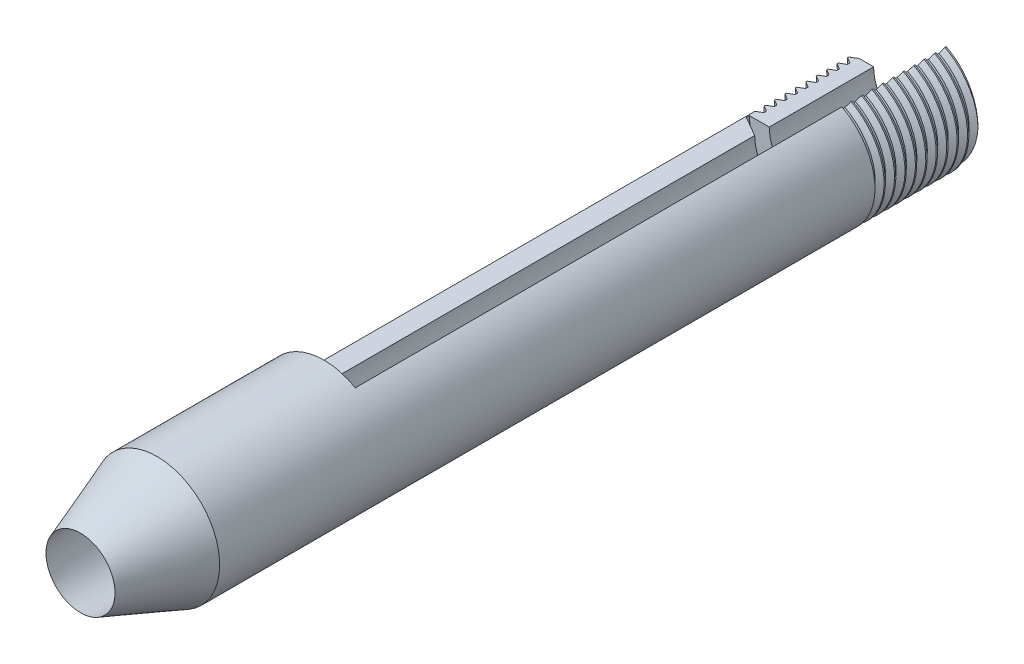
SolidWorks part; units mm, degrees
note: The reader was unsure of these and kept them because the rebuilt part matched: shared geometry of "Sketch2<8>", "Sketch2<12>".
ref_plane "Front Plane" through (0, 0, 0) normal (0, 0, 1) x (1, 0, 0)
ref_plane "Top Plane" through (0, 0, 0) normal (0, 1, 0) x (1, 0, 0)
ref_plane "Right Plane" through (0, 0, 0) normal (1, 0, 0) x (0, 0, -1)
sketch "Sketch2" plane through (0, 0, 0) normal (0, 1, 0) x (1, 0, 0)
  line L1 (-9, 0) -> (-9, -108.9955)
  line L2 (-4.958, -119.9955) -> (-9, -108.9955)
  line L4 (-6, 0) -> (-9, 0)
  line L5 (-6, -108.9955) -> (-4.958, -119.9955)
  line L6 (-8.85, -85.2806) -> (-6, -86.926)
  line L7 (0, 52.748) -> (0, -49947.252) construction
  line L9 (-6, -108.9955) -> (-6, 0)
  line L10 (-9, -15) -> (-6, -15)
  line L11 (-9, -85) -> (-6, -85)
  line L12 (-8.85, -85) -> (-8.85, -85.2806)
  line L13 (-8.85, -15.4482) -> (-6, -17.0937)
  line L14 (-8.85, -15) -> (-8.85, -15.4482)
  point P18 (0, 0)
  dimension "D1" = 120
  dimension "D2" = 11
  dimension "D3" = 6
  dimension "D4" = 70
  dimension "D5" = 3
  dimension "D6" = 15
  dimension "D7" = 20.176
  dimension "D8" = 30
  dimension "D9" = 0.15
  dimension "D10" = 30
revolve "Revolve2" add sketch "Sketch2" angle 360 about L7
revolve "Revolve3" add sketch "Sketch2<8>" angle 240 about L7
sketch "Sketch2<8>" plane through (0, 0, 0) normal (0, 1, 0) x (1, 0, 0) same geometry as "Sketch2"
revolve "Cut-Revolve19" cut sketch "Sketch2<12>" angle 60 about L7
sketch "Sketch2<12>" plane through (0, 0, 0) normal (0, 1, 0) x (1, 0, 0) same geometry as "Sketch2"
thread "Thread1" pitch 1.5 start angle 0, offset 1.5, length 0, pitch 1.5, diameter 18
ref_plane "Plane4" through (9, 0, -1.5) normal (0, -1, 0) x (1, 0, 0)
sketch "Thread Profile4" plane through (9, 0, -1.5) normal (0, -1, 0) x (1, 0, 0)
  line L0 (0, 0) -> (0, 1.5) construction
  line L11 (0, 0) -> (0, 1.3125)
  line L12 (0, 1.3125) -> (-0.8119, 0.8437)
  line L13 (-0.8119, 0.8437) -> (-0.8119, 0.4687)
  line L15 (-0.8119, 0.4687) -> (0, 0)
  line L17 (-0.8119, 0.6562) -> (0, 0.6562) construction
  point P2 (0, 0)
  dimension "Pitch" = 1.5
  dimension "Profile_Angle" = 60
  dimension "Profile_Land" = 0.375
  dimension "Profile_Height" = 0.8119
